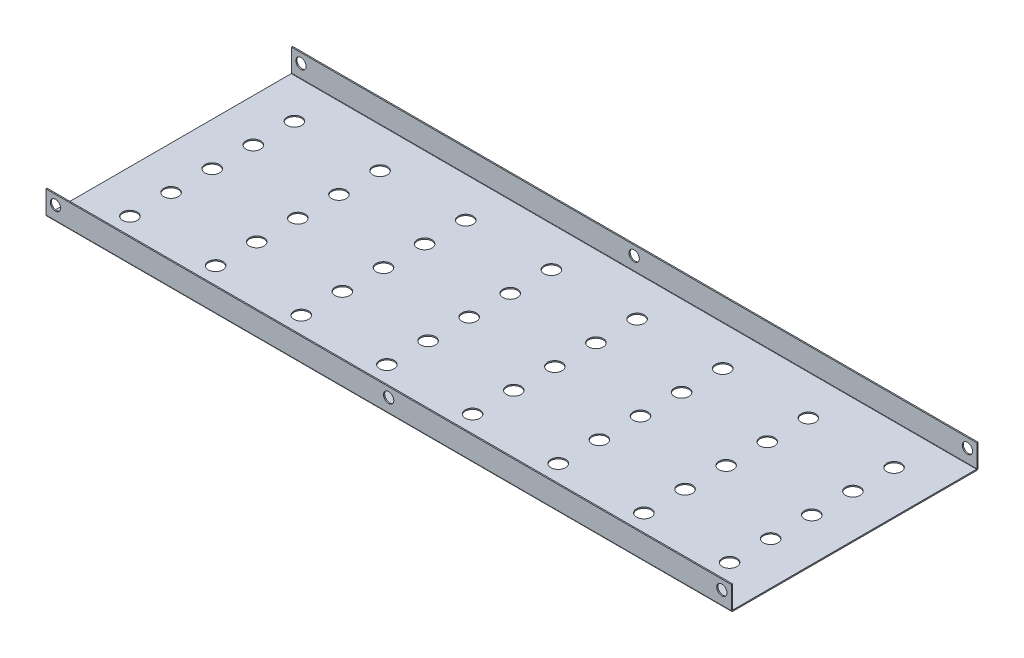
SolidWorks part; units mm, degrees
note: The reader was unsure of these and kept them because the rebuilt part matched: flange length of "边线-法兰1".
material "1023 碳钢板 (SS)"
ref_plane "前视基准面" through (0, 0, 0) normal (0, 0, 1) x (1, 0, 0)
ref_plane "上视基准面" through (0, 0, 0) normal (0, 1, 0) x (1, 0, 0)
ref_plane "右视基准面" through (0, 0, 0) normal (1, 0, 0) x (0, 0, -1)
sketch "草图1" plane through (0, 0, 0) normal (0, 1, 0) x (1, 0, 0)
  line L0 (-150, 72) -> (-150, -72) construction
  line L1 (-200, 72) -> (200, 72)
  line L2 (-200, 72) -> (-200, -72)
  line L3 (-200, -72) -> (200, -72)
  line L4 (200, 72) -> (200, -72)
  line L5 (-200, 72) -> (200, -72) construction
  line L6 (-200, -72) -> (200, 72) construction
  line L7 (-100, 72) -> (-100, -72) construction
  line L8 (-50, 72) -> (-50, -72) construction
  line L9 (0, 0) -> (0, -72) construction
  circle A0 centre (-175, -48) radius 4.25
  circle A1 centre (-175, -24) radius 4.25
  circle A2 centre (-175, 0) radius 4.25
  circle A3 centre (-175, 24) radius 4.25
  circle A4 centre (-175, 48) radius 4.25
  circle A5 centre (-125, -48) radius 4.25
  circle A6 centre (-125, -24) radius 4.25
  circle A7 centre (-125, 0) radius 4.25
  circle A8 centre (-125, 24) radius 4.25
  circle A9 centre (-125, 48) radius 4.25
  circle A20 centre (-75, -48) radius 4.25
  circle A21 centre (-25, -48) radius 4.25
  circle A22 centre (-25, -24) radius 4.25
  circle A23 centre (-75, -24) radius 4.25
  circle A24 centre (-75, 0) radius 4.25
  circle A25 centre (-25, 0) radius 4.25
  circle A26 centre (-75, 24) radius 4.25
  circle A27 centre (-25, 24) radius 4.25
  circle A28 centre (-25, 48) radius 4.25
  circle A29 centre (-75, 48) radius 4.25
  circle A30 centre (25, 48) radius 4.25
  circle A31 centre (25, 24) radius 4.25
  circle A32 centre (25, 0) radius 4.25
  circle A33 centre (25, -24) radius 4.25
  circle A34 centre (25, -48) radius 4.25
  circle A35 centre (75, -48) radius 4.25
  circle A36 centre (75, -24) radius 4.25
  circle A37 centre (75, 0) radius 4.25
  circle A38 centre (75, 24) radius 4.25
  circle A39 centre (75, 48) radius 4.25
  circle A40 centre (125, 48) radius 4.25
  circle A41 centre (125, 24) radius 4.25
  circle A42 centre (125, 0) radius 4.25
  circle A43 centre (125, -24) radius 4.25
  circle A44 centre (125, -48) radius 4.25
  circle A45 centre (175, -48) radius 4.25
  circle A46 centre (175, -24) radius 4.25
  circle A47 centre (175, 0) radius 4.25
  circle A48 centre (175, 24) radius 4.25
  circle A49 centre (175, 48) radius 4.25
  point P0 (0, 0)
  dimension "D5" = 8.5
  dimension "D6" = 24
  dimension "D11" = 25
  dimension "D1" = 400
  dimension "D2" = 144
  dimension "D3" = 24
  dimension "D4" = 25
  dimension "D7" = 24
  dimension "D8" = 24
  dimension "D9" = 24
  dimension "D10" = 24
  dimension "D12" = 25
  dimension "D13" = 25
  dimension "D14" = 25
  dimension "D15" = 50
  dimension "D16" = 50
  dimension "D17" = 50
base flange "基体-法兰1" sketch "草图1" thickness 0.7 reverse thickness direction no parameters "D1"=0.2
edge flange "边线-法兰1" sketch "草图12" flange profiles "草图12", "草图13" flange angle 90 flange length 14 flange position material inside bend radius 0.2 thickness 0.7 relief rectangular parameters "D6"=10, "D8"=1
sketch "草图12" plane through (0, 0, 72) normal (0, 0, 1) x (1, 0, 0)
  line L2 (-200, 0) -> (-200, 13.3)
  line L3 (-200, 13.3) -> (200, 13.3)
  line L4 (200, 13.3) -> (200, 0)
  line L11 (-200, 0) -> (200, 0) construction
  line L12 (-200, 0) -> (200, 0)
sketch "草图13" plane through (0, 0, -72) normal (0, 0, -1) x (-1, 0, 0)
  line L2 (-200, 0) -> (-200, 13.3)
  line L3 (-200, 13.3) -> (200, 13.3)
  line L4 (200, 13.3) -> (200, 0)
  line L7 (-200, 0) -> (200, 0) construction
  line L8 (-200, 0) -> (200, 0)
bend "边线折弯1" bend radius 0.2 bend angle 90 parameters "D5"=1
bend "边线折弯2" bend radius 0.2 bend angle 90 parameters "D5"=2
sketch "草图14" plane through (0, 0, 72) normal (0, 0, 1) x (1, 0, 0)
  line L0 (200, 13.3) -> (-200, 13.3) construction
  line L1 (-200, 13.3) -> (-200, 0.2) construction
  line L2 (0, 13.3) -> (0, 0) construction
  circle A0 centre (-194.5, 7.8) radius 3
  circle A1 centre (0, 7.8) radius 3
  circle A2 centre (194.5, 7.8) radius 3
  dimension "D1" = 5.5
  dimension "D2" = 5.5
  dimension "D3" = 6
  dimension "D4" = 6
  dimension "D5" = 5.5
extrude "切除-拉伸1" cut sketch "草图14" against normal blind 10
sketch "草图15" plane through (0, 0, -72) normal (0, 0, -1) x (-1, 0, 0)
  line L0 (-200, 13.3) -> (-200, 0.2) construction
  line L1 (200, 13.3) -> (-200, 13.3) construction
  line L2 (0, 13.3) -> (0, 0) construction
  circle A0 centre (-194.5, 7.8) radius 3
  circle A1 centre (0, 7.8) radius 3
  circle A2 centre (194.5, 7.8) radius 3
  dimension "D1" = 6
  dimension "D3" = 5.5
  dimension "D4" = 5.5
  dimension "D5" = 6
  dimension "D2" = 5.5
extrude "切除-拉伸2" cut sketch "草图15" against normal blind 10
sketch "折弯-线1" [suppressed] plane through (0, 0, 0) normal (0, 1, 0) x (1, 0, 0)
sketch "边界框1" [suppressed] plane through (0, 0, 0) normal (0, 1, 0) x (1, 0, 0)
sheet metal parameters "钣金6" thickness 0.7 parameters "D1"=0.2
flat pattern "平板型式6" [suppressed]
sketch "折弯-线2" plane through (0, 0, 0) normal (0, 1, 0) x (1, 0, 0)
sketch3d "边界框2" [suppressed]
  line L0 (200, -72, 0) -> (-200, -72, 0) construction
  line L1 (200, 72, 0) -> (-200, 72, 0) construction
  line L2 (200, -72, 0) -> (200, 72, 0) construction
  line L3 (-200, -72, 0) -> (-200, 72, 0) construction
sheet metal parameters "钣金7" thickness 0.7 parameters "D1"=0.2
flat pattern "平板型式6" [suppressed]
sketch "折弯-线2" plane through (0, 0, 0) normal (0, 1, 0) x (1, 0, 0)
sketch3d "边界框2" [suppressed]
  line L0 (200, -72, 0) -> (-200, -72, 0) construction
  line L1 (200, 72, 0) -> (-200, 72, 0) construction
  line L2 (200, -72, 0) -> (200, 72, 0) construction
  line L3 (-200, -72, 0) -> (-200, 72, 0) construction
bend of the flat pattern "展平-<边线折弯1>1"
bend of the flat pattern "展平-<边线折弯2>1"
sheet metal parameters "钣金8" thickness 0.7 parameters "D1"=0.2
flat pattern "平板型式6" [suppressed]
sketch "折弯-线2" plane through (0, 0, 0) normal (0, 1, 0) x (1, 0, 0)
sketch3d "边界框2" [suppressed]
  line L0 (200, -72, 0) -> (-200, -72, 0) construction
  line L1 (200, 72, 0) -> (-200, 72, 0) construction
  line L2 (200, -72, 0) -> (200, 72, 0) construction
  line L3 (-200, -72, 0) -> (-200, 72, 0) construction
bend of the flat pattern "展平-<边线折弯1>1"
bend of the flat pattern "展平-<边线折弯2>1"
sheet metal parameters "钣金9" thickness 0.7 parameters "D1"=0.2
flat pattern "平板型式6" [suppressed]
sketch "折弯-线2" plane through (0, 0, 0) normal (0, 1, 0) x (1, 0, 0)
sketch3d "边界框2" [suppressed]
  line L0 (200, -72, 0) -> (-200, -72, 0) construction
  line L1 (200, 72, 0) -> (-200, 72, 0) construction
  line L2 (200, -72, 0) -> (200, 72, 0) construction
  line L3 (-200, -72, 0) -> (-200, 72, 0) construction
bend of the flat pattern "展平-<边线折弯1>1"
bend of the flat pattern "展平-<边线折弯2>1"
